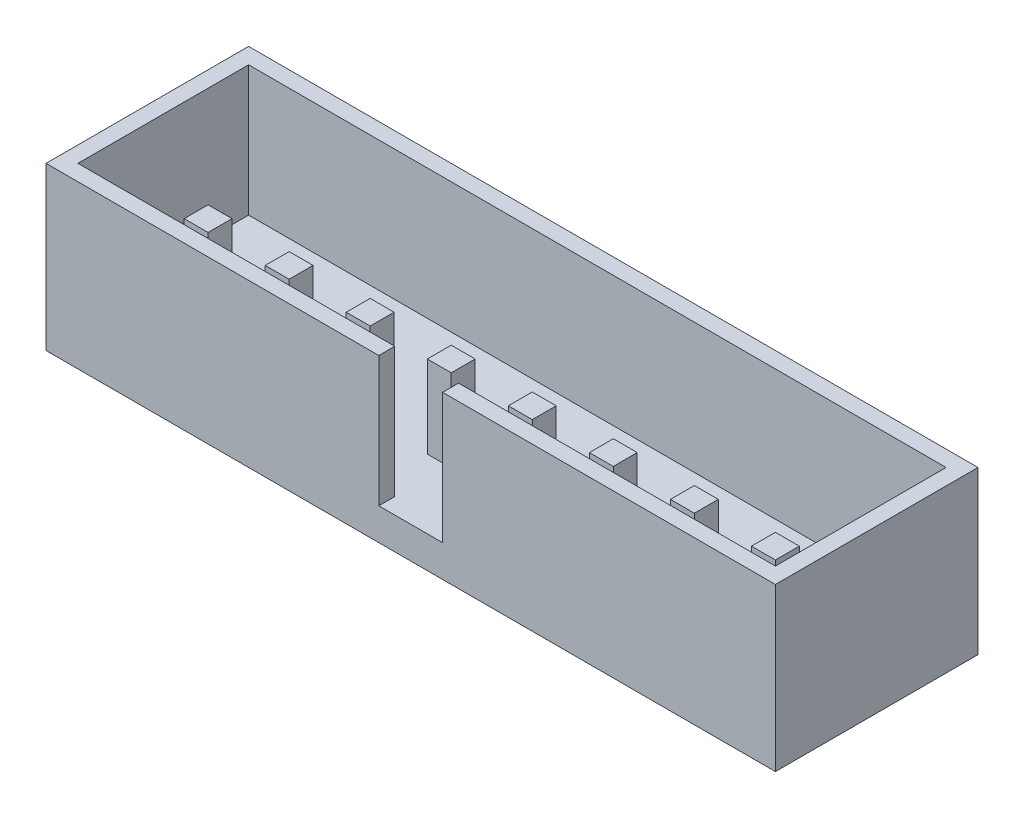
SolidWorks part; units mm, degrees
ref_plane "前视基准面" through (0, 0, 0) normal (0, 0, 1) x (1, 0, 0)
ref_plane "上视基准面" through (0, 0, 0) normal (0, 1, 0) x (1, 0, 0)
ref_plane "右视基准面" through (0, 0, 0) normal (1, 0, 0) x (0, 0, -1)
sketch "草图1" plane through (0, 0, 0) normal (0, 1, 0) x (1, 0, 0)
  line L0 (0, 7.1914) -> (0, -5.4429) construction
  line L1 (-11.43, 3.175) -> (11.43, 3.175)
  line L2 (-11.43, 3.175) -> (-11.43, -3.175)
  line L3 (-11.43, -3.175) -> (11.43, -3.175)
  line L4 (11.43, 3.175) -> (11.43, -3.175)
  line L5 (-10.6234, 0) -> (16.1963, 0) construction
  dimension "D1" = 22.86
  dimension "D2" = 6.35
extrude "拉伸1" add sketch "草图1" along normal blind 5.08
sketch "草图2" plane through (0, 5.08, 0) normal (0, 1, 0) x (-1, 0, 0)
  line L8 (10.93, -2.675) -> (10.93, 2.675)
  line L9 (10.93, 2.675) -> (-10.93, 2.675)
  line L10 (-10.93, 2.675) -> (-10.93, -2.675)
  line L11 (-10.93, -2.675) -> (10.93, -2.675)
  line L12 (10.93, -2.675) -> (10.93, 2.675)
  line L13 (10.93, 2.675) -> (-10.93, 2.675)
  line L14 (-10.93, 2.675) -> (-10.93, -2.675)
  line L15 (-10.93, -2.675) -> (10.93, -2.675)
  dimension "D1" = 0.5
extrude "切除-拉伸1" cut sketch "草图2" against normal offset from surface (4.08 mm away) 1 up to face at (0, 0, 0)
sketch "草图3" plane through (0, 0, 3.175) normal (0, 0, 1) x (1, 0, 0)
  line L0 (-11.43, 5.08) -> (11.43, 5.08) construction
  line L1 (-1, 5.08) -> (1, 5.08)
  line L2 (-1, 5.08) -> (-1, 1)
  line L3 (-1, 1) -> (1, 1)
  line L4 (1, 5.08) -> (1, 1)
  line L5 (10.93, 1) -> (-10.93, 1) construction
  line L6 (0, -1.5083) -> (0, 12.2426) construction
  dimension "D1" = 2
extrude "切除-拉伸2" cut sketch "草图3" against normal blind 1
sketch "草图4" plane through (0, 0, 0) normal (0, -1, 0) x (1, 0, 0)
  line L0 (7.6775, 0.635) -> (-8.5467, 0.635) construction
  line L1 (-11.43, 3.175) -> (11.43, 3.175) construction
  line L2 (0, -3.6953) -> (0, 4.0669) construction
  line L3 (-1.27, 2.1009) -> (-1.27, -0.7012) construction
  line L4 (-1.645, 1.01) -> (-0.895, 1.01)
  line L5 (-1.645, 1.01) -> (-1.645, 0.26)
  line L6 (-1.645, 0.26) -> (-0.895, 0.26)
  line L7 (-0.895, 1.01) -> (-0.895, 0.26)
  line L8 (0.895, 1.01) -> (1.645, 1.01)
  line L9 (0.895, 1.01) -> (0.895, 0.26)
  line L10 (0.895, 0.26) -> (1.645, 0.26)
  line L11 (1.645, 1.01) -> (1.645, 0.26)
  line L12 (2.54, -3.6953) -> (2.54, 4.0669) construction
  line L13 (3.435, 1.01) -> (4.185, 1.01)
  line L14 (3.435, 1.01) -> (3.435, 0.26)
  line L15 (3.435, 0.26) -> (4.185, 0.26)
  line L16 (4.185, 1.01) -> (4.185, 0.26)
  line L17 (5.08, -3.6953) -> (5.08, 4.0669) construction
  line L18 (5.975, 1.01) -> (6.725, 1.01)
  line L19 (5.975, 1.01) -> (5.975, 0.26)
  line L20 (5.975, 0.26) -> (6.725, 0.26)
  line L21 (6.725, 1.01) -> (6.725, 0.26)
  line L22 (7.62, -3.6953) -> (7.62, 4.0669) construction
  line L23 (-4.185, 1.01) -> (-3.435, 1.01)
  line L24 (-4.185, 1.01) -> (-4.185, 0.26)
  line L25 (-4.185, 0.26) -> (-3.435, 0.26)
  line L26 (-3.435, 1.01) -> (-3.435, 0.26)
  line L27 (-3.81, 2.1009) -> (-3.81, -0.7012) construction
  line L28 (5.1375, 0.635) -> (-11.0867, 0.635) construction
  line L29 (-6.725, 1.01) -> (-5.975, 1.01)
  line L30 (-6.725, 1.01) -> (-6.725, 0.26)
  line L31 (-6.725, 0.26) -> (-5.975, 0.26)
  line L32 (-5.975, 1.01) -> (-5.975, 0.26)
  line L33 (-6.35, 2.1009) -> (-6.35, -0.7012) construction
  line L34 (2.5975, 0.635) -> (-13.6267, 0.635) construction
  line L35 (8.515, 1.01) -> (9.265, 1.01)
  line L36 (8.515, 1.01) -> (8.515, 0.26)
  line L37 (8.515, 0.26) -> (9.265, 0.26)
  line L38 (9.265, 1.01) -> (9.265, 0.26)
  line L39 (10.16, -3.6953) -> (10.16, 4.0669) construction
  line L40 (-9.265, 1.01) -> (-8.515, 1.01)
  line L41 (-9.265, 1.01) -> (-9.265, 0.26)
  line L42 (-9.265, 0.26) -> (-8.515, 0.26)
  line L43 (-8.515, 1.01) -> (-8.515, 0.26)
  line L44 (-8.89, 2.1009) -> (-8.89, -0.7012) construction
  line L45 (0.0575, 0.635) -> (-16.1667, 0.635) construction
  dimension "D1" = 2.54
  dimension "D2" = 0.75
  dimension "D3" = 0.75
  dimension "D4" = 1.27
  dimension "D5" = 5
  dimension "D6" = 4
extrude "拉伸2" add sketch "草图4" along normal blind 2 and the other way offset from surface 1.5 other way up to face at (0, 5.08, 0.975)
